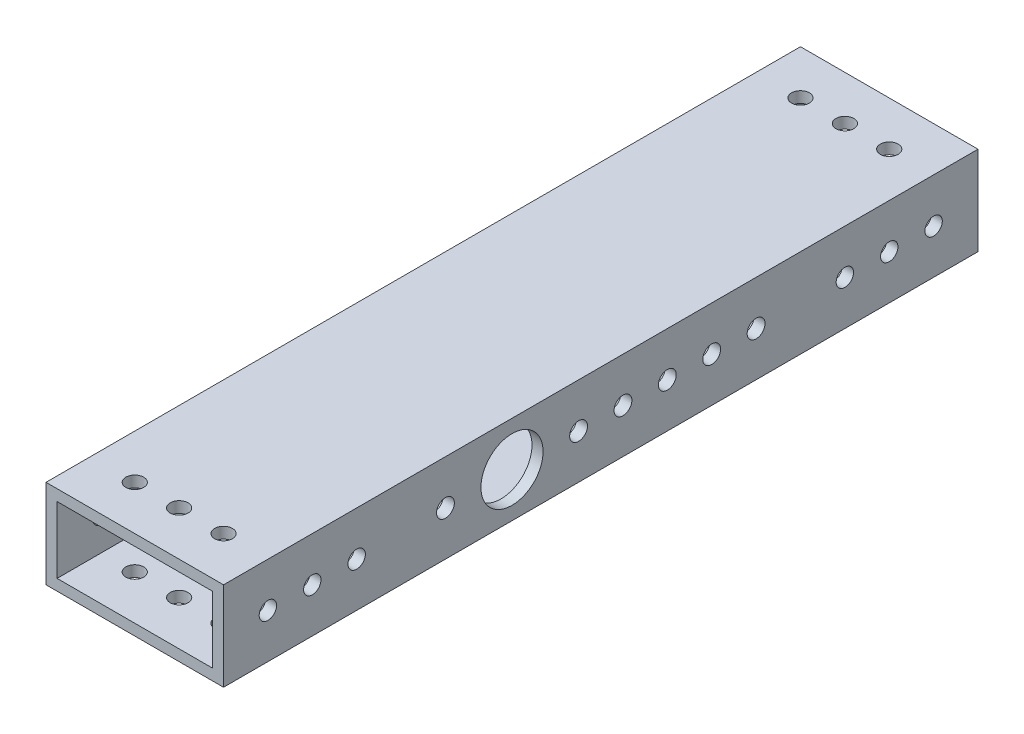
SolidWorks part; units mm, degrees
material "6061-T6 (SS)"
ref_plane "Front Plane" through (0, 0, 0) normal (0, 0, 1) x (1, 0, 0)
ref_plane "Top Plane" through (0, 0, 0) normal (0, 1, 0) x (1, 0, 0)
ref_plane "Right Plane" through (0, 0, 0) normal (1, 0, 0) x (0, 0, -1)
sketch "Sketch1" plane through (0, 0, 0) normal (0, 0, 1) x (1, 0, 0)
  line L0 (-22.225, 9.525) -> (22.225, 9.525)
  line L1 (-25.4, -12.7) -> (25.4, -12.7)
  line L2 (-25.4, -12.7) -> (-25.4, 12.7)
  line L3 (-25.4, 12.7) -> (25.4, 12.7)
  line L4 (25.4, -12.7) -> (25.4, 12.7)
  line L5 (-25.4, -12.7) -> (25.4, 12.7) construction
  line L6 (-25.4, 12.7) -> (25.4, -12.7) construction
  line L7 (22.225, -9.525) -> (22.225, 9.525)
  line L8 (-22.225, -9.525) -> (22.225, -9.525)
  line L9 (-22.225, -9.525) -> (-22.225, 9.525)
  point P0 (0, 0)
  dimension "D1" = 50.8
  dimension "D2" = 25.4
  dimension "D3" = 3.175
extrude "Boss-Extrude1" add sketch "Sketch1" along normal mid plane 215.9
sketch "Sketch3" plane through (0, 12.7, 0) normal (0, 1, 0) x (1, 0, 0)
  line L0 (-25.4, 0) -> (25.4, 0) construction
  line L1 (-25.4, -107.95) -> (-25.4, 107.95) construction
  line L2 (25.4, -107.95) -> (25.4, 107.95) construction
  line L3 (25.4, -107.95) -> (-25.4, -107.95) construction
  circle A0 centre (-12.7, -95.25) radius 2.5527
  circle A1 centre (0, -95.25) radius 2.5527
  circle A2 centre (12.7, -95.25) radius 2.5527
  circle A3 centre (12.7, 95.25) radius 2.5527
  circle A4 centre (0, 95.25) radius 2.5527
  circle A5 centre (-12.7, 95.25) radius 2.5527
  dimension "D1" = 5.1054
  dimension "D2" = 12.7
  dimension "D3" = 12.7
  dimension "D4" = 12.7
extrude "Cut-Extrude2" cut sketch "Sketch3" against normal through all
sketch "Sketch4" plane through (25.4, 0, 0) normal (1, 0, 0) x (0, 0, -1)
  line L0 (-25.4, 0) -> (-45.1908, 0) construction
  line L1 (-16.51, 0) -> (-34.29, 0) construction
  line L8 (-25.4, 0) -> (31.75, 0) construction
  line L9 (0, 12.7) -> (0, -12.7) construction
  line L10 (-107.95, 12.7) -> (107.95, 12.7) construction
  line L11 (-107.95, -12.7) -> (107.95, -12.7) construction
  circle A0 centre (-25.4, 0) radius 8.89
  circle A9 centre (31.75, 0) radius 2.5527
  circle A10 centre (19.05, 0) radius 2.5527
  dimension "D2" = 17.78
  dimension "D3" = 25.4
  dimension "D1" = 57.15
  dimension "D4" = 5.1054
  dimension "D6" = 44.45
extrude "Cut-Extrude3" cut sketch "Sketch4" against normal through all contours A0 | A9 | A10
sketch "Sketch2" plane through (25.4, 0, 0) normal (1, 0, 0) x (0, 0, -1)
  line L0 (-107.95, -12.7) -> (-107.95, 12.7) construction
  line L1 (0, 12.7) -> (0, -12.7) construction
  line L2 (-107.95, 12.7) -> (107.95, 12.7) construction
  line L3 (-107.95, -12.7) -> (107.95, -12.7) construction
  circle A0 centre (-95.25, 0) radius 2.4892
  circle A1 centre (95.25, 0) radius 2.4892
  circle A2 centre (-82.55, 0) radius 2.4892
  circle A3 centre (-69.85, 0) radius 2.4892
  circle A4 centre (69.85, 0) radius 2.4892
  circle A5 centre (82.55, 0) radius 2.4892
  dimension "D2" = 4.9784
  dimension "D5" = 4.9784
  dimension "D1" = 12.7
  dimension "D3" = 12.7
  dimension "D4" = 12.7
extrude "Cut-Extrude1" cut sketch "Sketch2" against normal through all
sketch "Sketch5" plane through (0, -12.7, 0) normal (0, -1, 0) x (1, 0, 0)
  line L0 (-25.4, 107.95) -> (-25.4, -107.95) construction
  line L1 (-25.4, 107.95) -> (25.4, 107.95) construction
  line L4 (25.4, 25.4) -> (-25.4, 25.4) construction
  line L5 (25.4, 107.95) -> (25.4, -107.95) construction
  circle A0 centre (-3.81, 69.85) radius 2.4892
  circle A1 centre (-16.51, 69.85) radius 2.4892
  circle A2 centre (-16.51, 57.15) radius 2.4892
  circle A3 centre (-3.81, 57.15) radius 2.4892
  circle A8 centre (-3.81, -6.35) radius 2.4892
  circle A9 centre (-16.51, -6.35) radius 2.4892
  circle A10 centre (-16.51, -19.05) radius 2.4892
  circle A11 centre (-3.81, -19.05) radius 2.4892
  dimension "D3" = 4.9784
  dimension "D4" = 8.89
  dimension "D7" = 12.7
  dimension "D12" = 82.55
  dimension "D5" = 31.75
  dimension "D6" = 12.7
  dimension "D1" = 2
  dimension "D2" = 2
extrude "Cut-Extrude4" cut sketch "Sketch5" against normal up to next
sketch "Sketch7" plane through (25.4, 0, 0) normal (1, 0, 0) x (0, 0, -1)
  circle A0 centre (44.45, 0) radius 2.5527
  circle A1 centre (31.75, 0) radius 2.5527 construction
  circle A5 centre (6.35, 0) radius 2.5527
  circle A6 centre (-6.35, 0) radius 2.5527
  circle A7 centre (-44.45, 0) radius 2.5527
  circle A8 centre (-25.4, 0) radius 8.89 construction
  dimension "D1" = 12.7
  dimension "D2" = 19.05
  dimension "D3" = 19.05
  dimension "D4" = 12.7
extrude "Cut-Extrude5" cut sketch "Sketch7" against normal up to next contours A0 | A7 | A6 | A5
